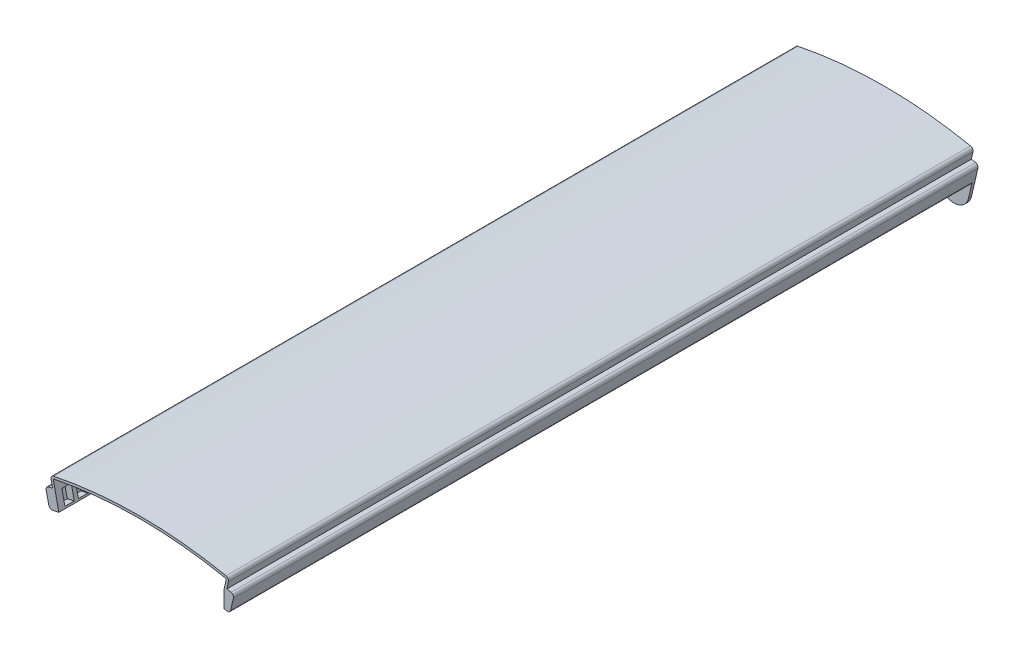
SolidWorks part; units mm, degrees
note: The reader was unsure of these and kept them because the rebuilt part matched: shared geometry of "Sketch1<3>", "Sketch1<4>", "Sketch1<5>", "Sketch1<6>".
ref_plane "Front Plane" through (0, 0, 0) normal (0, 0, 1) x (1, 0, 0)
ref_plane "Top Plane" through (0, 0, 0) normal (0, 1, 0) x (1, 0, 0)
ref_plane "Right Plane" through (0, 0, 0) normal (1, 0, 0) x (0, 0, -1)
sketch "Sketch1" plane through (0, 0, 0) normal (0, 0, 1) x (1, 0, 0)
  line L0 (0, 0) -> (0, -22221.0071) construction
  line L1 (0, 0) -> (22221.0071, 0) construction
  line L2 (0, 0) -> (-60.0619, 260.1568) construction
  line L3 (0, 0) -> (60.0619, 260.1568) construction
  line L4 (0, 0) -> (59.6707, 280.7284) construction
  line L5 (0, 0) -> (-59.6707, 280.7284) construction
  line L6 (59.6707, 280.7284) -> (58.2153, 273.8813)
  line L7 (-59.6707, 280.7284) -> (-58.2153, 273.8813)
  line L8 (60.0619, 260.1568) -> (62.9863, 272.8236)
  line L9 (-60.0619, 260.1568) -> (-62.9863, 272.8236)
  line L10 (-58.8761, 278.4333) -> (-57.8594, 273.6501)
  line L11 (-60.3071, 262.5524) -> (-62.1518, 270.5425)
  line L12 (58.8761, 278.4333) -> (57.8594, 273.6501)
  line L13 (60.3071, 262.5524) -> (62.1518, 270.5425)
  line L14 (59.8371, 260.5164) -> (59.0947, 257.301)
  line L15 (59.7696, 260.2243) -> (62.6265, 272.5986) construction
  line L16 (-59.3772, 280.7907) -> (-57.8594, 273.6501) construction
  line L17 (-59.8371, 260.5164) -> (-59.0947, 257.301)
  line L18 (-48.3097, 254.4547) -> (0, 0) construction
  line L19 (0, 0) -> (48.3097, 254.4547) construction
  line L20 (-59.0947, 257.301) -> (-57.97, 252.4292)
  line L21 (59.0947, 257.301) -> (57.97, 252.4292)
  line L22 (-38.5793, 256.1106) -> (-39.4183, 261.0406)
  line L23 (38.5793, 256.1106) -> (39.3241, 261.0548)
  line L24 (-59.8371, 260.5164) -> (-62.6265, 272.5986) construction
  line L25 (59.3148, 280.4971) -> (57.8594, 273.6501) construction
  line L26 (58.2781, 260.8764) -> (60.5928, 270.9024)
  line L27 (57.3111, 278.7659) -> (55.9604, 272.4115)
  line L28 (-57.3111, 278.7659) -> (-55.9604, 272.4115)
  line L29 (-58.2781, 260.8764) -> (-60.5928, 270.9024)
  line L30 (-55.9604, 272.4115) -> (-53.6525, 261.5538)
  line L31 (55.9604, 272.4115) -> (56.0535, 262.5838)
  line L32 (55.8029, 261.4103) -> (56.0535, 262.5838)
  line L33 (0.1, 264) -> (10, 284.9246)
  line L34 (-10, 284.9246) -> (-0.1, 264)
  line L35 (59.8371, 260.5164) -> (62.1518, 270.5425) construction
  line L36 (-59.8371, 260.5164) -> (-62.1518, 270.5425) construction
  line L37 (-60.3071, 262.5524) -> (-59.8371, 260.5164)
  line L38 (59.8371, 260.5164) -> (60.3071, 262.5524)
  arc A0 (60.0619, 260.1568) -> (-60.0619, 260.1568) centre (0, 0) ccw
  arc A1 (59.6707, 280.7284) -> (-59.6707, 280.7284) centre (0, 0) ccw
  arc A2 (62.9863, 272.8236) -> (58.2153, 273.8813) centre (0, 0) ccw
  arc A3 (-62.9863, 272.8236) -> (-58.2153, 273.8813) centre (0, 0) cw
  arc A4 (58.2153, 273.8813) -> (-58.2153, 273.8813) centre (0, 0) ccw construction
  arc A5 (-60.5603, 273.0651) -> (-57.8594, 273.6501) centre (0, 0) cw
  arc A6 (57.8068, 260.9745) -> (-57.8068, 260.9745) centre (0, 0) ccw
  arc A7 (57.2413, 280.9276) -> (-57.2413, 280.9276) centre (0, 0) ccw
  arc A8 (60.5603, 273.0651) -> (57.8594, 273.6501) centre (0, 0) ccw
  arc A9 (59.0947, 257.301) -> (-59.0947, 257.301) centre (0, 0) ccw
  arc A10 (60.1294, 260.4491) -> (-59.8371, 260.5164) centre (0, 0) ccw construction
  arc A11 (59.3148, 280.4971) -> (-59.6083, 280.4349) centre (0, 0) ccw construction
  circle A12 centre (-48.3097, 254.4547) radius 2
  circle A13 centre (48.3097, 254.4547) radius 2
  circle A14 centre (0, 0) radius 259 construction
  arc A15 (57.97, 252.4292) -> (38.5793, 256.1106) centre (48.3097, 254.4547) cw
  arc A16 (-57.97, 252.4292) -> (-38.5793, 256.1106) centre (-48.3097, 254.4547) ccw
  arc A17 (-62.6265, 272.5986) -> (-57.8594, 273.6501) centre (0, 0) cw construction
  arc A18 (-60.5603, 273.0651) -> (-62.1518, 270.5425) centre (-60.1056, 271.0149) ccw
  arc A19 (-58.8761, 278.4333) -> (-57.2413, 280.9276) centre (-56.822, 278.8699) cw
  arc A20 (62.6265, 272.5986) -> (57.8594, 273.6501) centre (0, 0) ccw construction
  arc A21 (60.5603, 273.0651) -> (62.1518, 270.5425) centre (60.1056, 271.0149) cw
  arc A22 (57.2413, 280.9276) -> (58.8761, 278.4333) centre (56.822, 278.8699) cw
  arc A23 (60.2139, 271.503) -> (60.5928, 270.9024) centre (60.1056, 271.0149) cw
  arc A24 (60.2139, 271.503) -> (55.9604, 272.4115) centre (0, 0) ccw
  arc A25 (56.9218, 279.3598) -> (57.3111, 278.7659) centre (56.822, 278.8699) cw
  arc A26 (56.9218, 279.3598) -> (-56.9218, 279.3598) centre (0, 0) ccw
  arc A27 (-57.3111, 278.7659) -> (-56.9218, 279.3598) centre (-56.822, 278.8699) cw
  arc A28 (-60.2139, 271.503) -> (-55.9604, 272.4115) centre (0, 0) cw
  arc A29 (-60.2139, 271.503) -> (-60.5928, 270.9024) centre (-60.1056, 271.0149) ccw
  arc A30 (60.1057, 261.686) -> (-60.1057, 261.686) centre (0, 0) ccw
  arc A31 (59.8371, 260.5164) -> (-59.8371, 260.5164) centre (0, 0) ccw construction
  arc A32 (57.8068, 260.9745) -> (60.3071, 262.5524) centre (58.2609, 263.0248) ccw
  arc A33 (-60.3071, 262.5524) -> (-57.8068, 260.9745) centre (-58.2609, 263.0248) ccw
  dimension "D7" = 280
  dimension "D10" = 264
  dimension "D13" = 4
  dimension "D14" = 4
  dimension "D15" = 518
  dimension "D16" = 2.1
  dimension "D24" = 2.1
  dimension "D1" = 267
  dimension "D2" = 12
  dimension "D3" = 13
  dimension "D4" = 13
  dimension "D5" = 12
  dimension "D6" = 287
  dimension "D11" = 10.75
  dimension "D12" = 10.75
  dimension "D19" = 0.95
  dimension "D20" = 10
  dimension "D21" = 0.1
  dimension "D22" = 10
  dimension "D23" = 0.1
  dimension "D8" = 0.3
  dimension "D9" = 0.3
  dimension "D17" = 1.6
  dimension "D18" = 1.2
extrude "Back" add sketch "Sketch1" against normal blind 2
extrude "Sides" add sketch "Sketch1<3>" along normal blind 492
sketch "Sketch1<3>" plane through (0, 0, 0) normal (0, 0, 1) x (1, 0, 0) same geometry as "Sketch1"
extrude "First notch" add sketch "Sketch1<4>" along normal blind 4.5 contours A30 L30 A28 A29 L29 | A30 L26 A23 A24 L31
sketch "Sketch1<4>" plane through (0, 0, 0) normal (0, 0, 1) x (1, 0, 0) same geometry as "Sketch1"
extrude "Second notch" add sketch "Sketch1<5>" along direction (0, 0, 1) on the side of the normal blind 2.8 from offset 10.7 contours A30 L30 A28 A29 L29 | A30 L26 A23 A24 L31
sketch "Sketch1<5>" plane through (0, 0, 0) normal (0, 0, 1) x (1, 0, 0) same geometry as "Sketch1"
pattern_linear "LPattern1" count 53 spacing 9 along (0, 0, 1) of "Second notch"
extrude "Boss-Extrude5" add sketch "Sketch1<6>" against normal blind 4.3 from vertex at 492 contours A30 L30 A28 A29 L29 | A30 L26 A23 A24 L31 starting at point (55.9604, 272.4115, 492)
sketch "Sketch1<6>" plane through (0, 0, 0) normal (0, 0, 1) x (1, 0, 0) same geometry as "Sketch1"
fillet "Fillet2" radius 2 4 edges at (0.1, 264, -1) (-0.1, 264, -1)
sketch "Sketch3" plane through (0, 0, 0) normal (0, 1, 0) x (1, 0, 0)
  line L1 (82.9413, -150) -> (-179.6109, -150)
  line L2 (82.9413, -150) -> (82.9413, -524.094)
  line L3 (82.9413, -524.094) -> (-179.6109, -524.094)
  line L4 (-179.6109, -150) -> (-179.6109, -524.094)
  dimension "D1" = 150
extrude "Cut-Extrude1" [suppressed] cut sketch "Sketch3" against normal through all both and the other way through all
